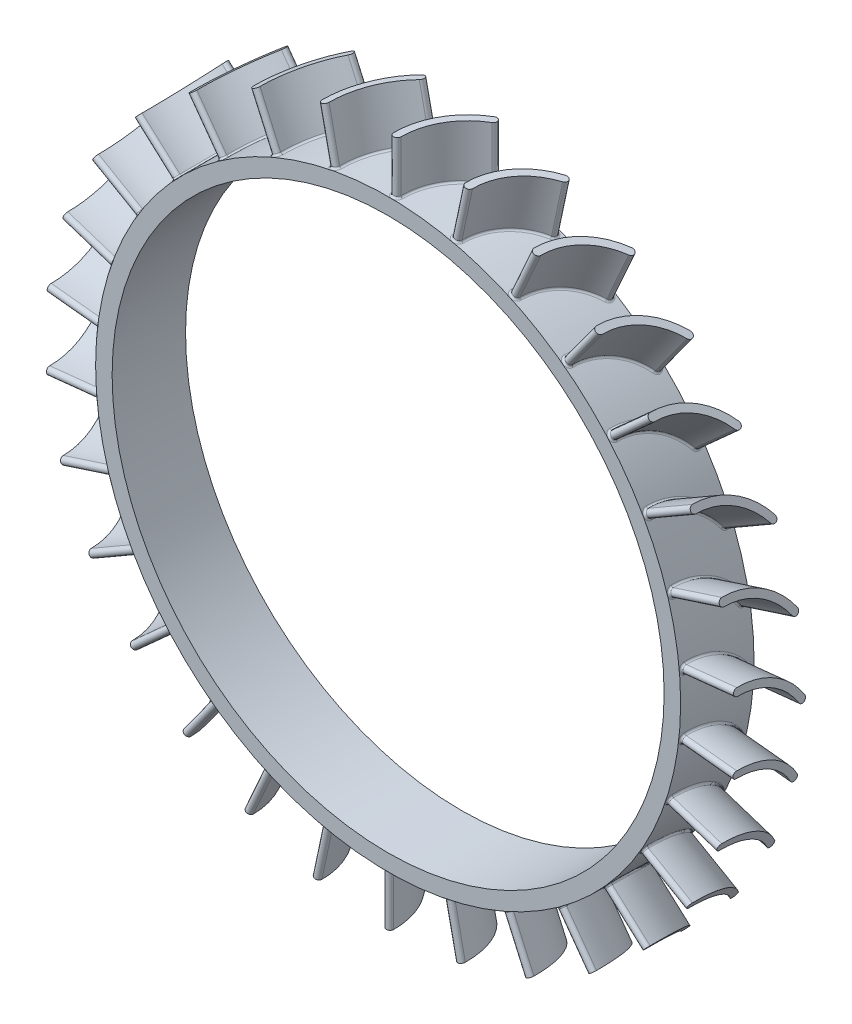
SolidWorks part; units mm, degrees
ref_plane "Front Plane" through (0, 0, 0) normal (0, 0, 1) x (1, 0, 0)
ref_plane "Top Plane" through (0, 0, 0) normal (0, 1, 0) x (1, 0, 0)
ref_plane "Right Plane" through (0, 0, 0) normal (1, 0, 0) x (0, 0, -1)
sketch "Sketch1" plane through (0, 0, 0) normal (0, 0, 1) x (1, 0, 0)
  circle A0 centre (0, 0) radius 75.19
  circle A1 centre (0, 0) radius 79.69
  dimension "D1" = 159.38
  dimension "D2" = 150.38
extrude "Boss-Extrude1" add sketch "Sketch1" along normal mid plane 20
sketch "Sketch2" plane through (0, 0, 0) normal (0, 1, 0) x (1, 0, 0)
  line L0 (-79.69, -10) -> (79.69, -10) construction
  line L1 (79.69, 10) -> (-79.69, 10) construction
  arc A0 (-0.0106, -8.5) -> (10, 9) centre (19.9887, -8.327) cw
  arc A1 (1.9893, -8.4827) -> (10.9989, 7.2673) centre (19.9887, -8.327) cw
  arc A2 (10, 9) -> (10.9989, 7.2673) centre (10.4994, 8.1336) cw
  arc A3 (-0.0106, -8.5) -> (1.9893, -8.4827) centre (0.9894, -8.4914) ccw
  dimension "D4" = 20
  dimension "D1" = 1.5
  dimension "D2" = 1
  dimension "D3" = 10
  dimension "D5" = 2
extrude "Boss-Extrude2" add sketch "Sketch2" along normal blind 17 from offset 77
fillet "Fillet1" radius 0.5 4 edges at (0.8842, 79.6851, 9.4858) (1.4308, 79.6772, 0.87) (9.602, 79.1094, -7.6925) (2.9985, 79.6336, 2.3829)
pattern_circular "CirPattern1" count 30 over 360 about axis through (0, 0, 10) along (0, 0, 1) of "Boss-Extrude2", "Fillet1"
